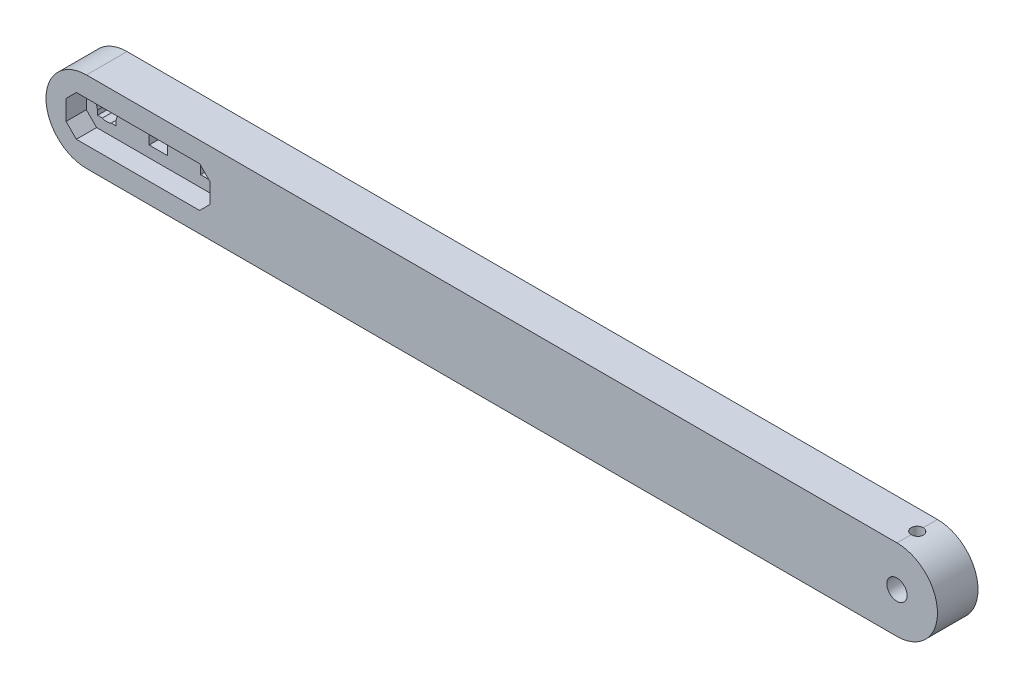
SolidWorks part; units mm, degrees
ref_plane "Front Plane" through (0, 0, 0) normal (0, 0, 1) x (1, 0, 0)
ref_plane "Top Plane" through (0, 0, 0) normal (0, 1, 0) x (1, 0, 0)
ref_plane "Right Plane" through (0, 0, 0) normal (1, 0, 0) x (0, 0, -1)
sketch "Sketch1" plane through (0, 0, 0) normal (0, 0, 1) x (1, 0, 0)
  line L0 (-100, 10) -> (100, 10)
  line L1 (-100, 10) -> (100, -10) construction
  line L2 (100, -10) -> (-100, -10)
  line L3 (-72.09, -5) -> (-69.55, -2.46)
  line L4 (-69.55, -2.46) -> (-69.55, 2.46)
  line L5 (-72.09, -5) -> (-102.51, -5)
  line L6 (-105.05, -2.46) -> (-105.05, 2.46)
  line L7 (-72.09, 5) -> (-102.51, 5)
  line L8 (-69.55, -5) -> (-105.05, 5) construction
  line L9 (-105.05, -5) -> (-69.55, 5) construction
  line L10 (-69.55, 2.46) -> (-72.09, 5)
  line L11 (-105.05, 2.46) -> (-102.51, 5)
  line L12 (-102.51, -5) -> (-105.05, -2.46)
  line L13 (-72.35, 2.25) -> (-76.85, 2.25)
  line L14 (-72.35, 2.25) -> (-72.35, -2.25)
  line L15 (-72.35, -2.25) -> (-76.85, -2.25)
  line L16 (-76.85, 2.25) -> (-76.85, -2.25)
  line L17 (-72.35, 2.25) -> (-76.85, -2.25) construction
  line L18 (-72.35, -2.25) -> (-76.85, 2.25) construction
  line L19 (-85.05, 2.25) -> (-89.55, 2.25)
  line L20 (-85.05, 2.25) -> (-85.05, -2.25)
  line L21 (-85.05, -2.25) -> (-89.55, -2.25)
  line L22 (-89.55, 2.25) -> (-89.55, -2.25)
  line L23 (-85.05, 2.25) -> (-89.55, -2.25) construction
  line L24 (-85.05, -2.25) -> (-89.55, 2.25) construction
  line L25 (-97.75, 2.25) -> (-102.25, 2.25)
  line L26 (-97.75, 2.25) -> (-97.75, -2.25)
  line L27 (-97.75, -2.25) -> (-102.25, -2.25)
  line L28 (-102.25, 2.25) -> (-102.25, -2.25)
  line L29 (-97.75, 2.25) -> (-102.25, -2.25) construction
  line L30 (-97.75, -2.25) -> (-102.25, 2.25) construction
  arc A0 (-100, 10) -> (-100, -10) centre (-100, 0) ccw
  circle A1 centre (100, 0) radius 2.5
  arc A2 (100, 10) -> (100, -10) centre (100, 0) cw
  circle A3 centre (-100, 0) radius 2.5
  point P2 (-74.6, 0)
  point P6 (-87.3, 0)
  point P23 (-87.3, 0)
  point P28 (-100, 0)
  dimension "D16" = 5
  dimension "D17" = 5
  dimension "D1" = 200
  dimension "D2" = 20
  dimension "D3" = 10
  dimension "D4" = 35.5
  dimension "D5" = 2.54
  dimension "D6" = 2.54
  dimension "D7" = 2.54
  dimension "D8" = 2.54
  dimension "D9" = 2.54
  dimension "D10" = 2.54
  dimension "D11" = 2.54
  dimension "D12" = 2.54
  dimension "D13" = 12.7
  dimension "D14" = 12.7
  dimension "D15" = 4.5
extrude "Boss-Extrude1" add sketch "Sketch1" along normal blind 10 contours A2 L0 A0 L2 A1 L5 L12 L6 L11 L7 L10 L4 L3 region at (7.0593, 0, 0)
extrude "Boss-Extrude2" add sketch "Sketch1<4>" along normal blind 5 contours L12 L5 L3 L4 L10 L7 L11 L6 L28 L25 L26 L27 L22 L19 L20 L21 L16 L13 L14 L15 region at (-87.3, -4.6312, 0)
sketch "Sketch1<4>" plane through (0, 0, 0) normal (0, 0, 1) x (1, 0, 0) same geometry as "Sketch1"
sketch "Sketch2" plane through (0, 10, 0) normal (0, 1, 0) x (1, 0, 0)
  line L0 (100, -10) -> (100, 0) construction
  circle A0 centre (100, -5) radius 1.5
  dimension "D1" = 3
extrude "Cut-Extrude1" cut sketch "Sketch2" against normal up to next
